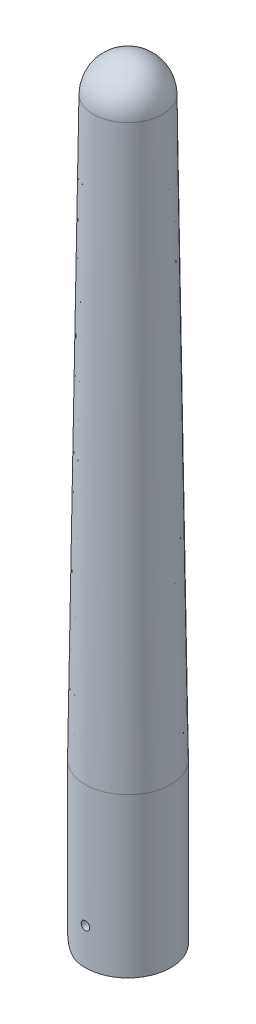
SolidWorks part; units mm, degrees
ref_plane "Front Plane" through (0, 0, 0) normal (0, 0, 1) x (1, 0, 0)
ref_plane "Top Plane" through (0, 0, 0) normal (0, 1, 0) x (1, 0, 0)
ref_plane "Right Plane" through (0, 0, 0) normal (1, 0, 0) x (0, 0, -1)
sketch "Sketch2" plane through (0, 0, 0) normal (0, 0, 1) x (1, 0, 0)
  line L0 (0, 0) -> (0, 105.1939) construction
  line L1 (0, 0) -> (5, 0)
  line L2 (5, 0) -> (5, 19.05)
  line L3 (5, 19.05) -> (4.0564, 86.424)
  line L4 (0, 90.424) -> (0, 0)
  arc A0 (4.0564, 86.424) -> (0, 90.424) centre (0, 86.3672) ccw
  dimension "D1" = 19.05
  dimension "D2" = 10
  dimension "D3" = 90.424
  dimension "D4" = 4
revolve "Revolve1" add sketch "Sketch2" angle 360 about L0
sketch "Sketch6" plane through (0, 0, 0) normal (0, 0, 1) x (1, 0, 0)
  line L1 (-4, 3.5) -> (-4, 7)
  line L3 (-5, 19.05) -> (-5, 0) construction
  line L4 (-5, 0) -> (-5, 8)
  line L5 (-4, 7) -> (-5, 8)
  line L6 (-5, 0) -> (5, 0) construction
  line L7 (-1, 0.5) -> (5, 0.5)
  line L8 (5, 0) -> (5, 19.05) construction
  line L9 (5, 0.5) -> (5, 0)
  line L10 (5, 0) -> (-5, 0)
  arc A0 (-1, 0.5) -> (-4, 3.5) centre (-1, 3.5) cw
  dimension "D1" = 45
  dimension "D2" = 1
  dimension "D3" = 4
  dimension "D4" = 8
  dimension "D5" = 0.5
extrude "Cut-Extrude1" cut sketch "Sketch6" against normal through all both and the other way through all
sketch "Sketch7" plane through (0, 0, 0) normal (0, 0, 1) x (1, 0, 0)
  circle A0 centre (0, 4.7625) radius 0.5
  dimension "D1" = 1
  dimension "D2" = 4.7625
extrude "Cut-Extrude2" cut sketch "Sketch7" against normal through all both and the other way through all
sketch "Sketch8" plane through (0, 0.5, 0) normal (0, -1, 0) x (1, 0, 0)
  line L0 (0, 3) -> (-5, 3)
  line L1 (-5, 3) -> (-5, -3)
  line L2 (-5, -3) -> (0, -3)
  arc A0 (0, -3) -> (0, 3) centre (0, 0) ccw
  arc A1 (-4, 3) -> (-4, -3) centre (0, 0) ccw construction
extrude "Cut-Extrude3" cut sketch "Sketch8" against normal up to vertex (6.5 mm away) up to point (-4, 7, 3)
